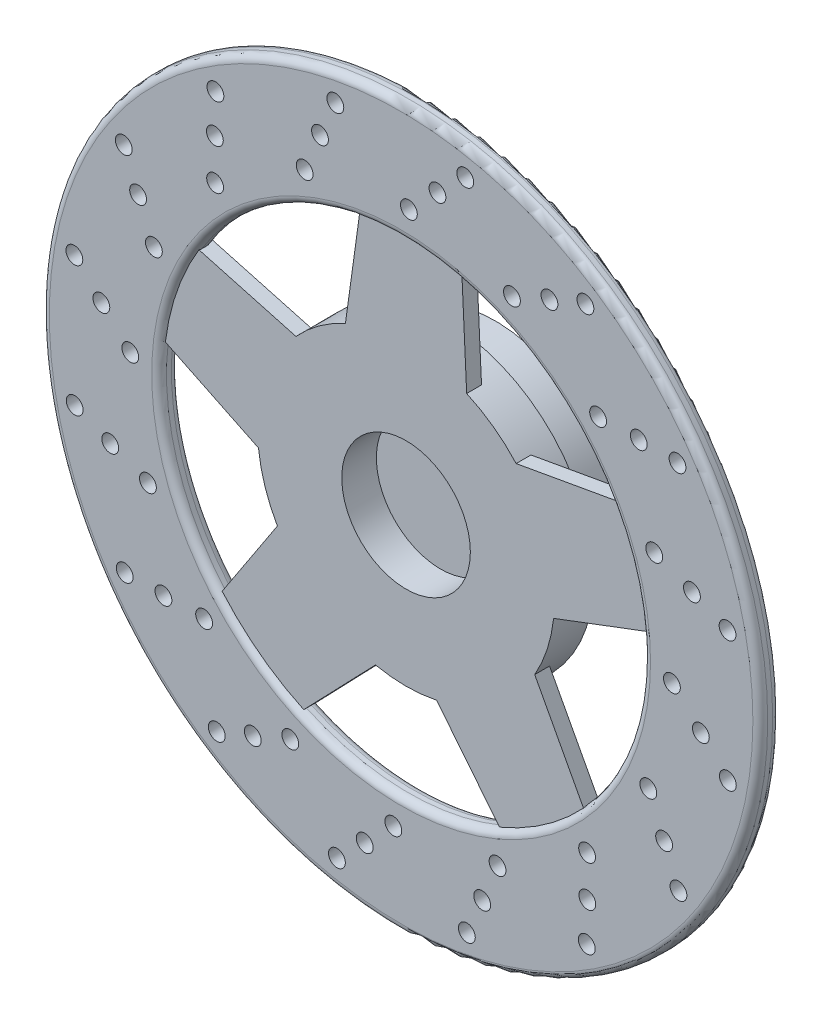
SolidWorks part; units mm, degrees
material "Stainless Steel (ferritic)"
ref_plane "Front Plane" through (0, 0, 0) normal (0, 0, 1) x (1, 0, 0)
ref_plane "Top Plane" through (0, 0, 0) normal (0, 1, 0) x (1, 0, 0)
ref_plane "Right Plane" through (0, 0, 0) normal (1, 0, 0) x (0, 0, -1)
sketch "Sketch1" plane through (0, 0, 0) normal (0, 0, 1) x (1, 0, 0)
  circle A0 centre (0, 0) radius 25
extrude "Boss-Extrude1" add sketch "Sketch1" along normal blind 10
sketch "Sketch2" plane through (0, 0, 10) normal (0, 0, 1) x (1, 0, 0)
  circle A0 centre (0, 0) radius 30
extrude "Boss-Extrude2" add sketch "Sketch2" along normal blind 5
sketch "Sketch3" plane through (0, 0, 15) normal (0, 0, 1) x (1, 0, 0)
  line L0 (-9.399, 48.0142) -> (-12.2552, 27.3827)
  line L1 (11.2985, 47.603) -> (12.2552, 27.3827)
  line L2 (42.7598, 23.7762) -> (22.2554, 20.1171)
  line L3 (48.7646, 3.9646) -> (29.8295, -3.1937)
  line L4 (35.826, -33.3197) -> (26.0098, -14.9496)
  line L5 (18.8397, -45.1528) -> (6.1805, -29.3565)
  line L6 (-20.6181, -44.3689) -> (-6.1805, -29.3565)
  line L7 (-37.121, -31.8706) -> (-26.0098, -14.9496)
  line L8 (-48.5687, 5.8982) -> (-29.8295, -3.1937)
  line L9 (-41.7817, 25.4557) -> (-22.2554, 20.1171)
  circle A0 centre (0, 0) radius 30
  circle A1 centre (0, 0) radius 72.616
  circle A2 centre (0, 0) radius 48.9255
  point P27 (0, 0)
  circle M1 centre (0, 0) radius 30
  dimension "D1" = 5
extrude "Boss-Extrude3" add sketch "Sketch3" along normal blind 4 contours A1 A2 | L9 A2 L8 M1 | L7 A2 L6 M1 | L5 A2 L4 M1 | L3 A2 L2 M1 | L1 A2 L0 M1 | M1 region at (0.4813, 38.5791, 15) region at (0, 0, 15) region at (-36.5422, 12.3794, 15) region at (36.8397, 11.4639, 15) region at (-23.0656, -30.9283, 15) region at (22.2869, -31.4941, 15) region at (-70.5621, 0, 15)
sketch "Sketch4" plane through (0, 0, 19) normal (0, 0, 1) x (1, 0, 0)
  circle A0 centre (0, 0) radius 48.9255
extrude "Cut-Extrude1" cut sketch "Sketch4" against normal blind 1
fillet "Fillet1" radius 1.5 8 edges at (-46.822, -14.1916, 15) (-0.9718, -48.9158, 15) (46.2214, -16.04, 15) (29.5382, 39.0026, 15) (-27.9658, 40.1449, 15) (48.9255, 0, 19) (72.616, 0, 19) (72.616, 0, 15)
sketch "Sketch5" plane through (0, 0, 18) normal (0, 0, 1) x (1, 0, 0)
  circle A0 centre (0, 0) radius 13
extrude "Cut-Extrude2" cut sketch "Sketch5" against normal blind 7
sketch "Sketch6" plane through (0, 0, 19) normal (0, 0, 1) x (1, 0, 0)
  circle A0 centre (-19.4979, 51.1802) radius 1.7
  circle A1 centre (-16.3955, 58.7952) radius 1.7
  circle A2 centre (-13.2931, 65.9873) radius 1.7
extrude "Cut-Extrude3" cut sketch "Sketch6" against normal blind 14
pattern_circular "CirPattern1" count 16 over 360 about axis through (0, 0, 19) along (0, 0, 1) of "Cut-Extrude3"
